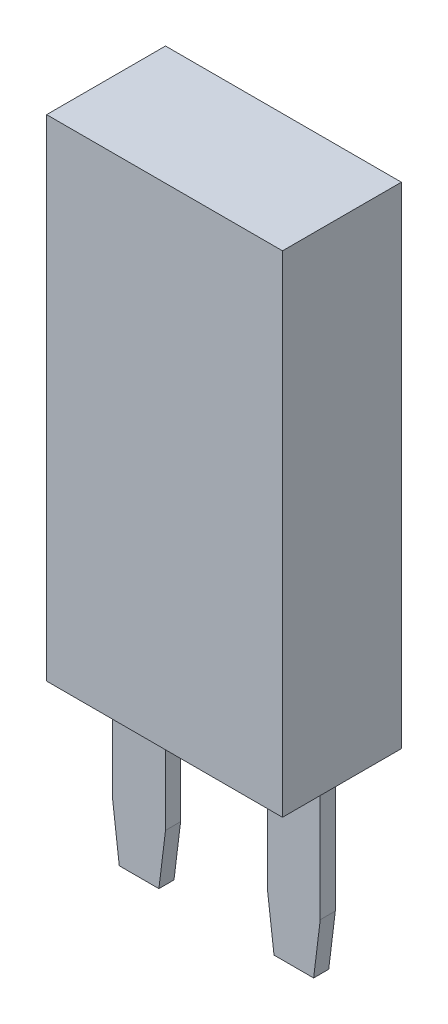
SolidWorks part; units mm, degrees
ref_plane "Front Plane" through (0, 0, 0) normal (0, 0, 1) x (1, 0, 0)
ref_plane "Top Plane" through (0, 0, 0) normal (0, 1, 0) x (1, 0, 0)
ref_plane "Right Plane" through (0, 0, 0) normal (1, 0, 0) x (0, 0, -1)
sketch "Sketch1" plane through (0, 0, 0) normal (0, 0, 1) x (1, 0, 0)
  line L1 (-6.25, 13) -> (6.25, 13)
  line L2 (-6.25, 13) -> (-6.25, -13)
  line L3 (-6.25, -13) -> (6.25, -13)
  line L4 (6.25, 13) -> (6.25, -13)
  line L5 (-6.25, 13) -> (6.25, -13) construction
  line L6 (-6.25, -13) -> (6.25, 13) construction
  point P0 (0, 0)
  dimension "D1" = 26
  dimension "D2" = 12.5
extrude "Boss-Extrude1" add sketch "Sketch1" along normal mid plane 6.3
sketch "Sketch2" plane through (0, -13, 0) normal (0, -1, 0) x (1, 0, 0)
  line L0 (0, 3.9068) -> (0, -3.8663) construction
  line L1 (2.7, 0.4) -> (2.7, -0.4)
  line L2 (-5.5, 0.4) -> (-2.7, 0.4)
  line L3 (-5.5, 0.4) -> (-5.5, -0.4)
  line L4 (-5.5, -0.4) -> (-2.7, -0.4)
  line L5 (-2.7, 0.4) -> (-2.7, -0.4)
  line L6 (5.5, -0.4) -> (2.7, -0.4)
  line L7 (5.5, 0.4) -> (5.5, -0.4)
  line L8 (5.5, 0.4) -> (2.7, 0.4)
  point P7 (-2.7, 0)
  dimension "D1" = 2.8
  dimension "D2" = 0.8
  dimension "D3" = 11
extrude "Boss-Extrude2" add sketch "Sketch2" along normal blind 9.3
chamfer "Chamfer1" distance 0.35 angle 83 4 edges at (5.5, -22.3, 0) (2.7, -22.3, 0) (-2.7, -22.3, 0) (-5.5, -22.3, 0) first distance on face at (4.1, -22.3, 0) first distance on face at (-4.1, -22.3, 0)
